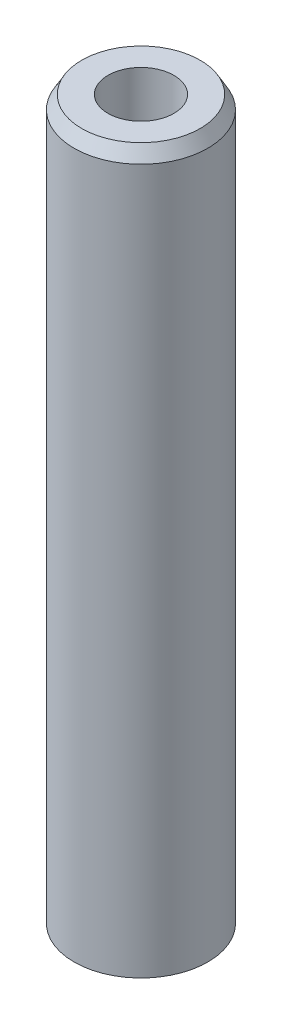
SolidWorks part; units mm, degrees
ref_plane "Front Plane" through (0, 0, 0) normal (0, 0, 1) x (1, 0, 0)
ref_plane "Top Plane" through (0, 0, 0) normal (0, 1, 0) x (1, 0, 0)
ref_plane "Right Plane" through (0, 0, 0) normal (1, 0, 0) x (0, 0, -1)
sketch "Sketch1" plane through (0, 0, 0) normal (0, 1, 0) x (1, 0, 0)
  circle A0 centre (0, 0) radius 30
  dimension "SHAFT_OD" = 60
extrude "Boss-Extrude1" add sketch "Sketch1" along normal blind 325.5111
sketch "Sketch2" plane through (0, 0, 0) normal (0, 1, 0) x (1, 0, 0)
  circle A0 centre (0, 0) radius 14.7936
  dimension "BORE_D" = 29.5873
extrude "Cut-Extrude1" cut sketch "Sketch2" along normal through all
chamfer "Chamfer1" distance 5.9533 angle 30 2 edges at (0, 325.5111, 30) (0, 0, 30) first distance on face at (0, 325.5111, 30) first distance on face at (0, 0, 14.7936)
